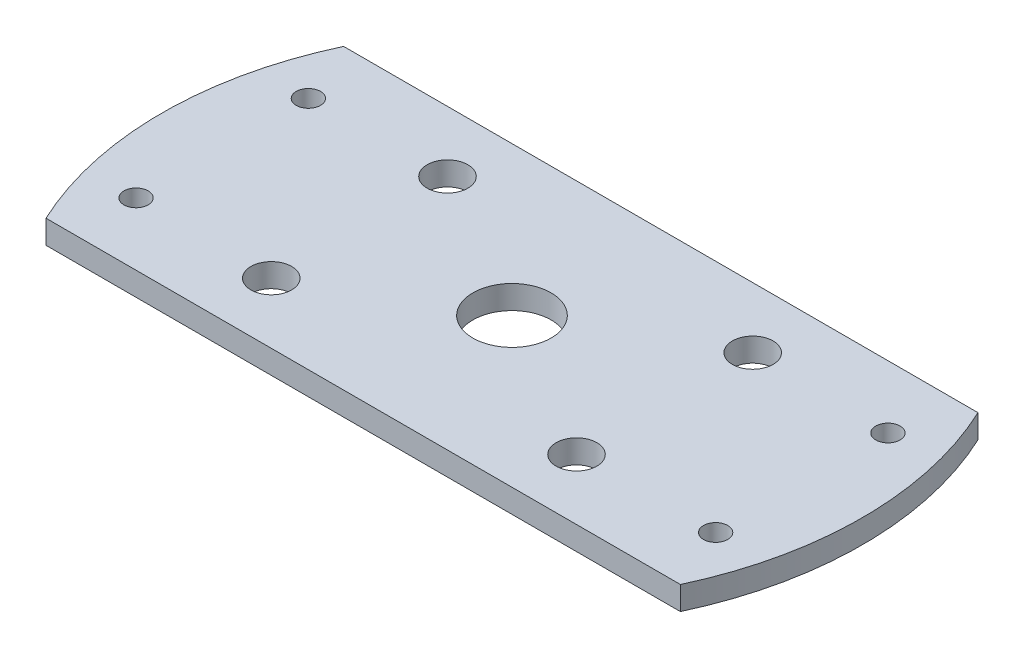
SolidWorks part; units mm, degrees
material "Thornel Mat VMA"
ref_plane "Front Plane" through (0, 0, 0) normal (0, 0, 1) x (1, 0, 0)
ref_plane "Top Plane" through (0, 0, 0) normal (0, 1, 0) x (1, 0, 0)
ref_plane "Right Plane" through (0, 0, 0) normal (1, 0, 0) x (0, 0, -1)
sketch "Sketch1" plane through (0, 0, 0) normal (0, 1, 0) x (1, 0, 0)
  line L0 (0, 0) -> (0, 56.5511) construction
  line L1 (0, 0) -> (118.6796, 0) construction
  line L2 (-62, 19) -> (62, 19)
  line L5 (-62, -19) -> (62, -19)
  line L6 (62, 19) -> (62, 13)
  line L7 (62, 13) -> (59, 13)
  line L8 (59, 13) -> (59, -13)
  line L9 (62, -13) -> (59, -13)
  line L10 (62, -19) -> (62, -13)
  line L11 (-62, -19) -> (-62, -13)
  line L12 (-62, -13) -> (-59, -13)
  line L13 (-59, 13) -> (-59, -13)
  line L14 (-62, 13) -> (-59, 13)
  line L15 (-62, 19) -> (-62, 13)
  circle A0 centre (37, 11) radius 1.55
  circle A1 centre (-37, 11) radius 1.55
  circle A2 centre (-37, -11) radius 1.55
  circle A3 centre (37, -11) radius 1.55
  circle A4 centre (0, 0) radius 5
  circle A5 centre (20, 0) radius 1.55 construction
  circle A6 centre (-20, 0) radius 1.55 construction
  circle A7 centre (35, 0) radius 6 construction
  circle A8 centre (-35, 0) radius 6 construction
  circle A9 centre (28.5, 9) radius 1.55 construction
  circle A10 centre (28.5, -9) radius 1.55 construction
  circle A11 centre (-28.5, -9) radius 1.55 construction
  circle A12 centre (-28.5, 9) radius 1.55 construction
  point P13 (0, 19)
  point P18 (-61, 0)
  point P19 (61, 0)
  point P28 (59, 0)
  dimension "D1" = 3.1
  dimension "D2" = 22
  dimension "D3" = 8
  dimension "D4" = 3.1
  dimension "D5" = 10
  dimension "D6" = 20
  dimension "D11" = 35
  dimension "D12" = 12
  dimension "D13" = 8.5
  dimension "D14" = 2
  dimension "D7" = 38
  dimension "D8" = 124
  dimension "D9" = 3
  dimension "D10" = 6
extrude "Boss-Extrude1" add sketch "Sketch1" along normal blind 3
fillet "Fillet1" radius 3 8 edges at (-62, 1.5, -19) (-62, 1.5, -13) (-62, 1.5, 13) (-62, 1.5, 19) (62, 1.5, 19) (62, 1.5, 13) (62, 1.5, -13) (62, 1.5, -19)
sketch "草图4" plane through (0, 0, 0) normal (0, -1, 0) x (1, 0, 0)
  line L0 (0, 0) -> (0, 63.4958) construction
  line L1 (-45, 19) -> (-45, -19)
  line L2 (-59, 19) -> (59, 19) construction
  line L3 (59, -19) -> (-59, -19) construction
  line L4 (-45, -19) -> (-67.4332, -19)
  line L5 (-67.4332, -19) -> (-67.4332, 19)
  line L6 (-67.4332, 19) -> (-45, 19)
  line L7 (67.4332, 19) -> (45, 19)
  line L8 (67.4332, -19) -> (67.4332, 19)
  line L9 (45, -19) -> (67.4332, -19)
  line L10 (45, 19) -> (45, -19)
  dimension "D1" = 45
extrude "切除-拉伸1" cut sketch "草图4" against normal blind 10
sketch "草图6" plane through (0, 3, 0) normal (0, 1, 0) x (1, 0, 0)
  line L1 (45, 19) -> (-45, 19) construction
  line L2 (-45, -19) -> (45, -19) construction
  line L3 (-40.5, -19) -> (-45, -19)
  line L4 (-45, -19) -> (-45, 19)
  line L5 (-45, 19) -> (-40.5, 19)
  line L6 (0, 0) -> (0, 31.3174) construction
  line L7 (45, 19) -> (40.5, 19)
  line L8 (45, -19) -> (45, 19)
  line L9 (40.5, -19) -> (45, -19)
  circle A0 centre (0, 0) radius 44.7353 construction
  arc A1 (-40.5, 19) -> (-40.5, -19) centre (0, 0) ccw
  arc A2 (40.5, 19) -> (40.5, -19) centre (0, 0) cw
extrude "切除-拉伸2" cut sketch "草图6" against normal blind 10
sketch "草图7" plane through (0, 0, 0) normal (0, -1, 0) x (1, 0, 0)
  line L0 (0, 0) -> (0, -31.3174) construction
  circle A0 centre (0, -22.5) radius 2.6
  circle A1 centre (-19.4856, -11.25) radius 2.6
  circle A2 centre (-19.4856, 11.25) radius 2.6
  circle A3 centre (0, 22.5) radius 2.6
  circle A4 centre (19.4856, 11.25) radius 2.6
  circle A5 centre (19.4856, -11.25) radius 2.6
  point P18 (0, 0)
  dimension "D3" = 5.2
  dimension "D1" = 22.5
  dimension "D2" = 6
extrude "切除-拉伸3" cut sketch "草图7" against normal blind 10
